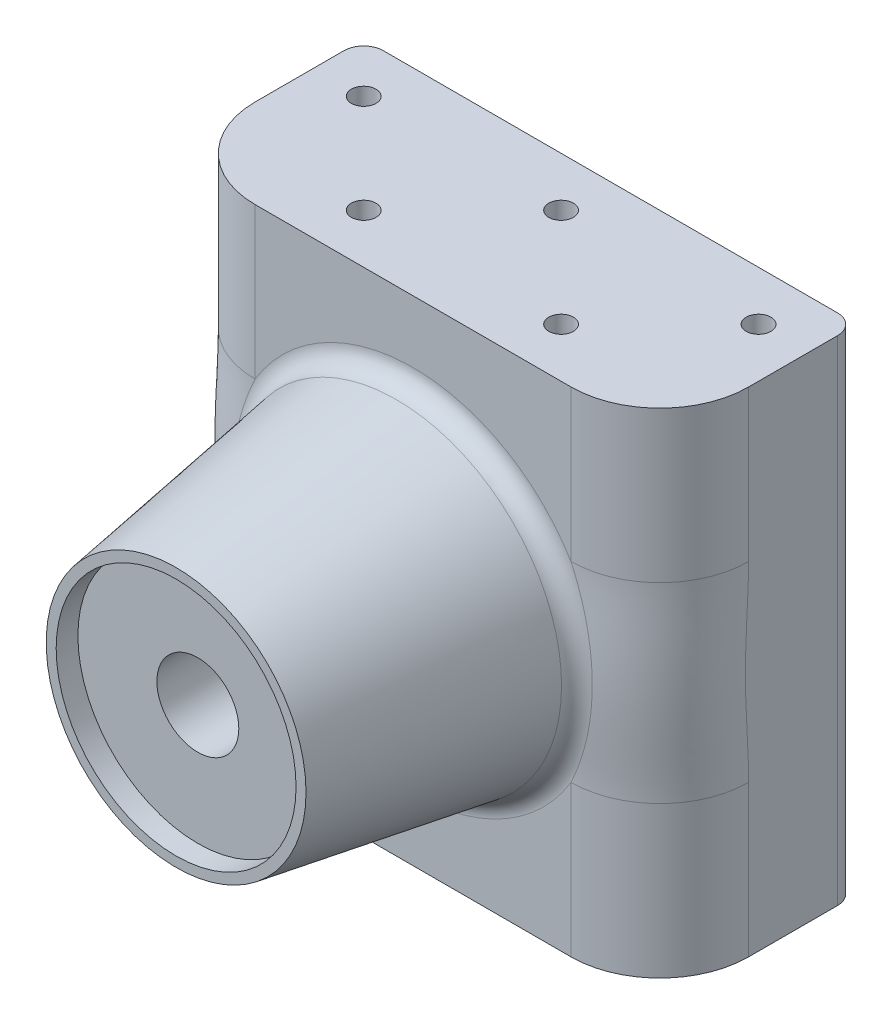
SolidWorks part; units mm, degrees
ref_plane "Спереди" through (0, 0, 0) normal (0, 0, 1) x (1, 0, 0)
ref_plane "Сверху" through (0, 0, 0) normal (0, 1, 0) x (1, 0, 0)
ref_plane "Справа" through (0, 0, 0) normal (1, 0, 0) x (0, 0, -1)
sketch "Эскиз1" plane through (0, 0, 0) normal (0, 0, 1) x (1, 0, 0)
  line L0 (0, 37) -> (0, -13) construction
  line L1 (-25, 37) -> (25, 37)
  line L2 (-25, 37) -> (-25, -13)
  line L3 (-25, -13) -> (25, -13)
  line L4 (25, 37) -> (25, -13)
  line L6 (-25, 0) -> (25, 0) construction
  dimension "D1" = 50
  dimension "D2" = 37
  dimension "D3" = 13
extrude "тело" add sketch "Эскиз1" against normal blind 20
sketch "Эскиз2" plane through (0, 0, 0) normal (0, 0, 1) x (1, 0, 0)
  line L0 (-25, -13) -> (25, -13) construction
  line L2 (25, -13) -> (25, 37) construction
  circle A0 centre (0, 12) radius 13
  point P10 (0, -13)
  point P13 (25, 12)
  dimension "D1" = 26
extrude "утолщение оси" add sketch "Эскиз2" along normal blind 24
sketch "Эскиз4" plane through (0, 0, 24) normal (0, 0, 1) x (1, 0, 0)
  circle A0 centre (0, 12) radius 4.15
  circle A1 centre (0, 12) radius 13 construction
  dimension "D1" = 8.3
extrude "ось вращения" cut sketch "Эскиз4" against normal through all
sketch "Эскиз8" plane through (0, 0, 24) normal (0, 0, 1) x (1, 0, 0)
  circle A0 centre (0, 12) radius 12.15
  dimension "D1" = 24.3
extrude "углубление под шайбу" cut sketch "Эскиз8" against normal blind 2.2
sketch "Эскиз9" plane through (0, 0, -20) normal (0, 0, -1) x (-1, 0, 0)
  line L1 (7.7365, 12) -> (3.8682, 18.7)
  line L2 (3.8682, 18.7) -> (-3.8682, 18.7)
  line L3 (-3.8682, 18.7) -> (-7.7365, 12)
  line L4 (-7.7365, 12) -> (-3.8682, 5.3)
  line L5 (-3.8682, 5.3) -> (3.8682, 5.3)
  line L6 (3.8682, 5.3) -> (7.7365, 12)
  circle A0 centre (0, 12) radius 6.7 construction
  dimension "D1" = 13.4
extrude "углубление под шестигр головку" cut sketch "Эскиз9" against normal blind 7
chamfer "Фаска2" distance 4 distance2 25 1 edges at (13, 12, 0) first distance on face at (13, 12, 0)
fillet "Скругление5" radius 2 1 edges at (17, 12, 0)
sketch "Эскиз7" plane through (0, 37, 0) normal (0, 1, 0) x (1, 0, 0)
  line L0 (-25, 5) -> (25, 5) construction
  line L3 (0, 20) -> (0, 0) construction
  line L4 (25, 20) -> (-25, 20) construction
  line L5 (25, 0) -> (-25, 0) construction
  circle A0 centre (-10, 5) radius 1.25
  circle A1 centre (10, 5) radius 1.25
  circle A2 centre (-20, 15) radius 1.25
  circle A3 centre (0, 15) radius 1.25
  circle A4 centre (20, 15) radius 1.25
  dimension "D1" = 2.5
  dimension "D4" = 10
  dimension "D2" = 20
  dimension "D3" = 5
  dimension "D5" = 20
  dimension "D6" = 20
extrude "Отверстия для шурупов снизу" cut sketch "Эскиз7" against normal blind 9
sketch "Эскиз10" [suppressed] plane through (0, -13, 0) normal (0, -1, 0) x (1, 0, 0)
  line L0 (16.2656, 0) -> (-16.2656, 0) construction
  circle A0 centre (-10, -8) radius 1.25
  circle A1 centre (10, -8) radius 1.25
  dimension "D1" = 8
  dimension "D2" = 2.5
extrude "Отверстия для шурупов сверху" [suppressed] cut sketch "Эскиз10" against normal blind 12
fillet "Скругление7" radius 2 2 edges at (25, 12, -20) (-25, 12, -20)
fillet "Скругление8" radius 9 2 edges at (25, 12, 0) (-25, 12, 0)
ref_plane "Плоскость1" through (0, 12, 0) normal (0, 1, 0) x (1, 0, 0)
mirror "Зеркальное отражение1" about plane through (0, 12, 0) normal (0, 1, 0) of "Отверстия для шурупов снизу"
chamfer "Фаска4" [suppressed] distance 10 distance2 1
